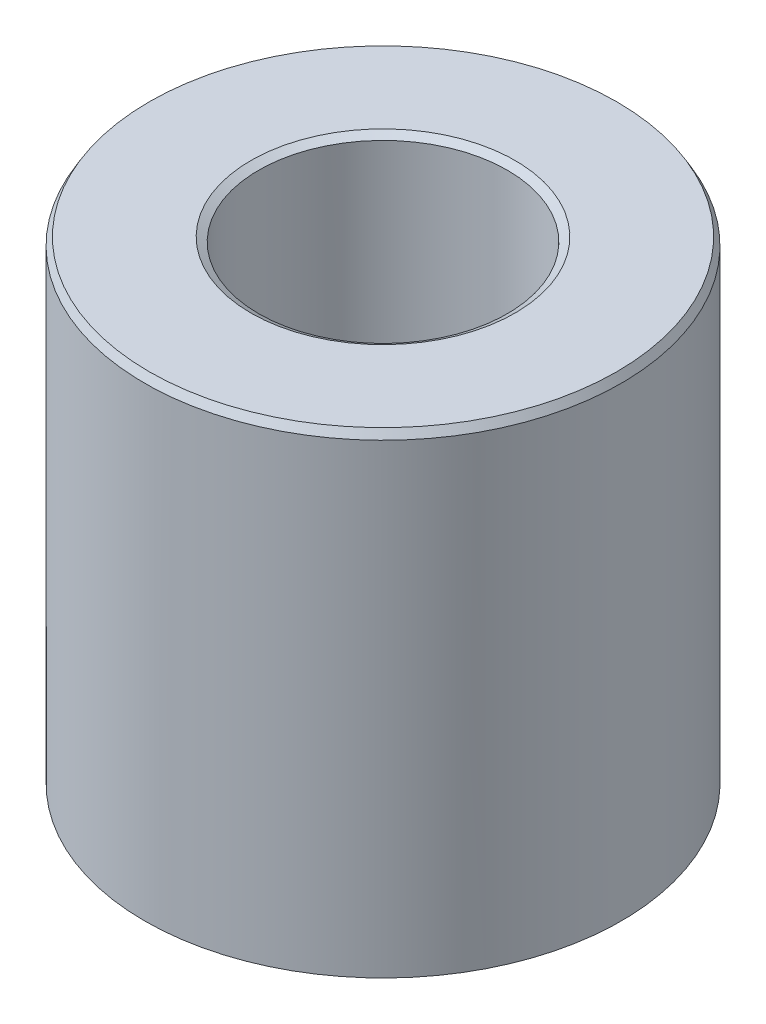
SolidWorks part; units mm, degrees
ref_plane "Front Plane" through (0, 0, 0) normal (0, 0, 1) x (1, 0, 0)
ref_plane "Top Plane" through (0, 0, 0) normal (0, 1, 0) x (1, 0, 0)
ref_plane "Right Plane" through (0, 0, 0) normal (1, 0, 0) x (0, 0, -1)
sketch "Sketch1" plane through (0, 0, 0) normal (0, 1, 0) x (1, 0, 0)
  circle A0 centre (0, 0) radius 20
  dimension "SLEEVE_OD" = 40
extrude "Boss-Extrude1" add sketch "Sketch1" along normal blind 40.1169
sketch "Sketch2" plane through (0, 0, 0) normal (0, 1, 0) x (1, 0, 0)
  circle A0 centre (0, 0) radius 10.4379
  dimension "BORE_D" = 20.8758
extrude "Cut-Extrude1" cut sketch "Sketch2" along normal through all
chamfer "Chamfer1" distance 0.6528 angle 30 4 edges at (0, 40.1169, 10.4379) (0, 0, 10.4379) (0, 0, 20) (0, 40.1169, 20) first distance on face at (0, 40.1169, 10.4379) first distance on face at (0, 0, 10.4379) first distance on face at (0, 40.1169, 20)
